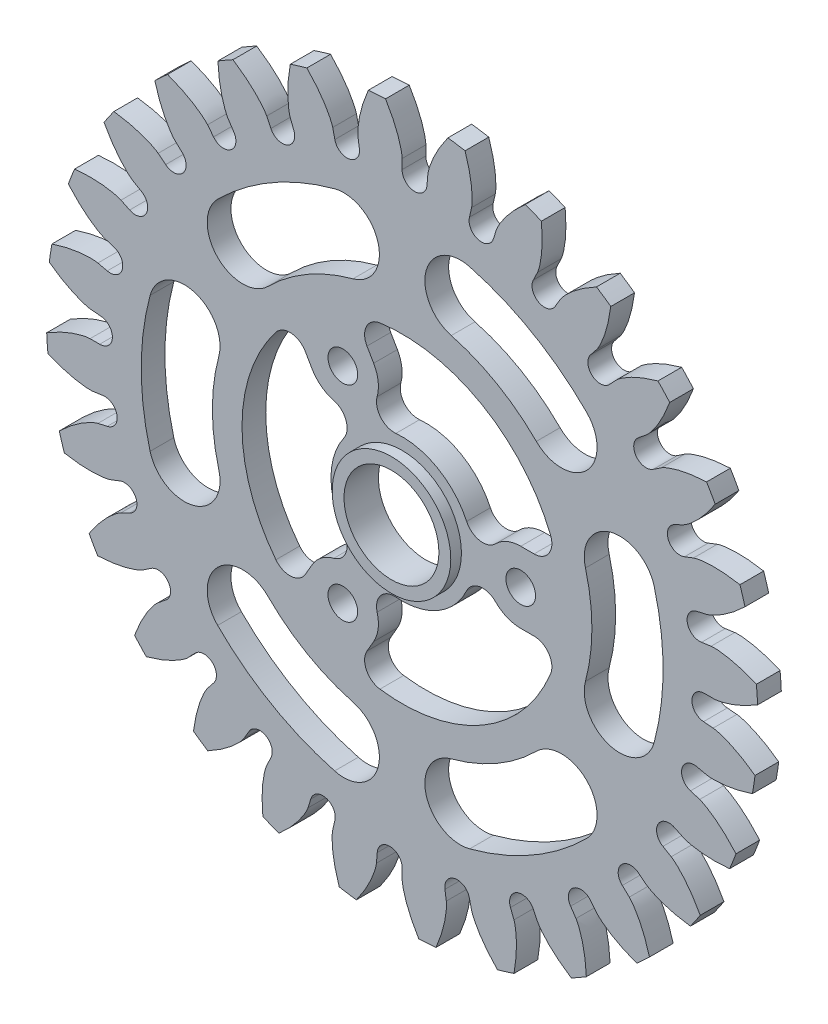
SolidWorks part; units mm, degrees
material "A2017"
ref_plane "正面" through (0, 0, 0) normal (0, 0, 1) x (1, 0, 0)
ref_plane "平面" through (0, 0, 0) normal (0, 1, 0) x (1, 0, 0)
ref_plane "右側面" through (0, 0, 0) normal (1, 0, 0) x (0, 0, -1)
sketch "ｽｹｯﾁ1" plane through (0, 0, 0) normal (1, 0, 0) x (0, 0, -1)
  line L0 (0, 0) -> (5.1985, 0) construction
  line L1 (0, 4) -> (2.9, 4)
  line L2 (2.9, 4) -> (2.9, 17.5)
  line L3 (2.9, 17.5) -> (0.9, 17.5)
  line L4 (0.9, 17.5) -> (0.9, 5)
  line L5 (0.9, 5) -> (0, 5)
  line L6 (0, 5) -> (0, 4)
  dimension "D1" = 35
  dimension "D2" = 2.9
  dimension "D3" = 2
  dimension "D4" = 10
  dimension "D5" = 8
revolve "回転1" add sketch "ｽｹｯﾁ1" angle 360 about L0
hole_wizard "M3 ねじ穴1" positions "ｽｹｯﾁ2" profile "ｽｹｯﾁ3" tap size "M3" standard "JIS" end condition through all
sketch "ｽｹｯﾁ2" plane through (0, 0, -0.9) normal (0, 0, 1) x (1, 0, 0)
  point P0 (10, 0)
  point P3 (-5, 8.6603)
  point P6 (-5, -8.6603)
sketch "ｽｹｯﾁ3" plane through (10, 0, -0.9) normal (1, 0, 0) x (0, -1, 0)
  line L0 (0, 0) -> (0, 2)
  line L1 (0, 2) -> (1.25, 2)
  line L2 (1.25, 2) -> (1.25, 0)
  line L5 (1.25, 0) -> (0, 0)
  line L11 (0, -6.35) -> (0, 107.95) construction
  dimension "次ｻｰﾌｪｽまでのねじ下穴ﾄﾞﾘﾙ直径" = 2.5
  dimension "次ｻｰﾌｪｽまでのねじ下穴ﾄﾞﾘﾙの深さ" = 2
cosmetic thread "穴のねじ山1" parameters "D2"=3
cosmetic thread "穴のねじ山2" parameters "D2"=3
cosmetic thread "穴のねじ山3" parameters "D2"=3
sketch "ｽｹｯﾁ4" plane through (0, 0, -0.9) normal (0, 0, 1) x (1, 0, 0)
  line L0 (10, 0) -> (13.5, 0) construction
  line L1 (10, 3) -> (13.5, 3)
  line L2 (10, -3) -> (13.5, -3)
  line L3 (-5, -8.6603) -> (-6.75, -11.6913) construction
  line L4 (-2.4019, -10.1603) -> (-4.1519, -13.1913)
  line L5 (-7.5981, -7.1603) -> (-9.3481, -10.1913)
  line L6 (-5, 8.6603) -> (-6.75, 11.6913) construction
  line L7 (-7.5981, 7.1603) -> (-9.3481, 10.1913)
  line L8 (-2.4019, 10.1603) -> (-4.1519, 13.1913)
  line L9 (0, 0) -> (10, 0) construction
  circle A0 centre (0, 0) radius 13.5
  arc A1 (10, 3) -> (10, -3) centre (10, 0) ccw
  arc A2 (13.5, -3) -> (13.5, 3) centre (13.5, 0) ccw
  arc A3 (-2.4019, -10.1603) -> (-7.5981, -7.1603) centre (-5, -8.6603) ccw
  arc A4 (-9.3481, -10.1913) -> (-4.1519, -13.1913) centre (-6.75, -11.6913) ccw
  arc A5 (-7.5981, 7.1603) -> (-2.4019, 10.1603) centre (-5, 8.6603) ccw
  arc A6 (-4.1519, 13.1913) -> (-9.3481, 10.1913) centre (-6.75, 11.6913) ccw
  circle A7 centre (0, 0) radius 6
  arc A8 (5.44, 2.5311) -> (7.8667, 2.1092) centre (6.8, 3.1639) ccw
  arc A9 (5.44, -2.5311) -> (7.8667, -2.1092) centre (6.8, -3.1639) cw
  arc A10 (-4.912, -3.4456) -> (-5.76, -5.7581) centre (-6.14, -4.307) cw
  arc A11 (-0.528, -5.9767) -> (-2.1067, -7.8674) centre (-0.66, -7.4709) ccw
  arc A12 (-0.528, 5.9767) -> (-2.1067, 7.8674) centre (-0.66, 7.4709) cw
  arc A13 (-4.912, 3.4456) -> (-5.76, 5.7581) centre (-6.14, 4.307) ccw
  point P6 (11.75, 0)
  point P15 (-5.875, -10.1758)
  point P22 (-5.875, 10.1758)
  point P34 (0, 0)
  point P49 (0, 0)
  dimension "D1" = 27
  dimension "D4" = 12
  dimension "D5" = 3
  dimension "D2" = 6
  dimension "D3" = 3
  dimension "D6" = 3
extrude "ｶｯﾄ - 押し出し1" cut sketch "ｽｹｯﾁ4" against normal through all contours A7 A13 A5 L7 A0 L5 A3 A10 | A12 A7 A8 A1 L1 A0 L8 A5 | A7 A11 A3 L4 A0 L2 A1 A9 region at (4.6223, 8.0061, -0.9) region at (4.6223, -8.0061, -0.9) region at (-9.2446, 0, -0.9)
fillet "ﾌｨﾚｯﾄ1" radius 1.5 6 edges at (13.1624, 3, -1.9) (-9.1793, -9.899, -1.9) (13.1624, -3, -1.9) (-3.9831, -12.899, -1.9) (-9.1793, 9.899, -1.9) (-3.9831, 12.899, -1.9)
sketch "歯車作図" plane through (0, 0, -0.9) normal (0, 0, 1) x (1, 0, 0)
  line L0 (0, 0) -> (25.5, 0) construction
  line L1 (25.5, 0) -> (26.3114, 0)
  line L2 (0, 0) -> (29.9745, -1.2355)
  circle A0 centre (0, 0) radius 30
  circle A1 centre (0, 0) radius 28 construction
  circle A2 centre (0, 0) radius 26.3114 construction
  circle A3 centre (0, 0) radius 25.5 construction
  arc A4 (27.9762, -1.1531) -> (27.9969, 0.4173) centre (0, 0) ccw
  spline S0 degree 4 poles (26.3114, 0) (26.3519, 0.0013) (26.4329, 0.0063) (26.6589, 0.033) (27.0848, 0.1166) (27.7247, 0.3006) (28.5755, 0.6367) (29.6254, 1.1673) (30.7905, 1.9033) (31.9912, 2.8259) (33.1927, 3.9303) (34.3032, 5.1257) (35.3247, 6.3978) (36.3053, 7.8011) (37.4014, 9.6156) (38.528, 11.8801) (39.5864, 14.6214) (40.4562, 17.7686) (41.0337, 20.9817) (41.3324, 24.232) (41.3656, 27.4956) (41.1738, 30.3444) (40.8594, 32.7708) (40.5015, 34.7769) (40.1586, 36.3716) (39.762, 37.9517) (39.3106, 39.5208) (38.8102, 41.0681) (38.3238, 42.4169) (37.8838, 43.5452) (37.5131, 44.4365) (37.2634, 45.0171) (36.9734, 45.666) (36.7803, 46.0867) (36.463, 46.7613) (36.2065, 47.2825) (35.8912, 47.9127) (35.6004, 48.4699) (35.2823, 49.0677) (34.9714, 49.6307) (34.7238, 50.0704) (34.5624, 50.3492) (34.4786, 50.4938) knots 0 0 0 0 0 0.002802 0.005604 0.015718 0.02996 0.048734 0.068727 0.096889 0.125051 0.153212 0.181374 0.209535 0.237696 0.271429 0.327752 0.384075 0.440398 0.496721 0.553044 0.609367 0.66569 0.693852 0.722013 0.750174 0.778336 0.806497 0.834659 0.86282 0.876901 0.890982 0.900036 0.909091 0.920455 0.931818 0.943182 0.954545 0.965909 0.977273 0.988636 1 1 1 1 1 construction
  spline S1 degree 4 poles (26.3114, 0) (26.3519, 0.0013) (26.4329, 0.0063) (26.6589, 0.033) (27.0848, 0.1166) (27.7247, 0.3006) (28.5755, 0.6367) (29.6254, 1.1673) (30.7905, 1.9033) (31.9912, 2.8259) (33.1927, 3.9303) (34.3032, 5.1257) (35.3247, 6.3978) (36.3053, 7.8011) (37.4014, 9.6156) (38.528, 11.8801) (39.5864, 14.6214) (40.4562, 17.7686) (41.0337, 20.9817) (41.3324, 24.232) (41.3656, 27.4956) (41.1738, 30.3444) (40.8594, 32.7708) (40.5015, 34.7769) (40.1586, 36.3716) (39.762, 37.9517) (39.3106, 39.5208) (38.8102, 41.0681) (38.3238, 42.4169) (37.8838, 43.5452) (37.5131, 44.4365) (37.2634, 45.0171) (37.049, 45.4967) (36.9499, 45.7154) (36.9004, 45.8237) knots 0 0 0 0 0 0.002802 0.005604 0.015718 0.02996 0.048734 0.068727 0.096889 0.125051 0.153212 0.181374 0.209535 0.237696 0.271429 0.327752 0.384075 0.440398 0.496721 0.553044 0.609367 0.66569 0.693852 0.722013 0.750174 0.778336 0.806497 0.834659 0.86282 0.876901 0.890982 0.900036 0.909091 0.909091 0.909091 0.909091 0.909091
  point P12 (0, 0)
  point P13 (29.9967, 0.4471)
  point P16 (0, 0)
  point P17 (29.9967, -1.5884)
  dimension "歯先円直径" = 60
  dimension "基礎ピッチ円直径" = 56
  dimension "基礎円直径" = 52.6228
  dimension "全歯丈" = 4.5
  dimension "基準ピッチ" = 1.5708
sketch "ｽｹｯﾁ6" plane through (0, 0, -0.9) normal (0, 0, 1) x (1, 0, 0)
  circle A0 centre (0, 0) radius 30 construction
  circle A1 centre (0, 0) radius 30
  circle A3 centre (0, 0) radius 17.5
  circle A4 centre (0, 0) radius 17.5
  dimension "D1" = 0
extrude "ﾎﾞｽ - 押し出し1" add sketch "ｽｹｯﾁ6" against normal through all
sketch "ｽｹｯﾁ7" plane through (0, 0, -0.9) normal (0, 0, 1) x (1, 0, 0)
  line L0 (25.5, 0) -> (26.3114, 0) construction
  line L1 (0, 0) -> (29.9745, -1.2355) construction
  line L2 (25.5, 0) -> (26.3114, 0)
  line L3 (25.4784, -1.0502) -> (29.9745, -1.2355)
  circle A1 centre (0, 0) radius 30
  arc A2 (29.9745, -1.2355) -> (29.9674, 1.3986) centre (0, 0) ccw
  circle A3 centre (0, 0) radius 25.5 construction
  arc A4 (25.4784, -1.0502) -> (25.5, 0) centre (0, 0) ccw
  spline S0 degree 4 poles (18.0064, -999.7701) (20.0439, 38.1516) (22.4374, 0.7712) (24.776, -0.3364) (27.0848, 0.1166) (27.7247, 0.3006) (28.5755, 0.6367) (29.6254, 1.1673) (30.7905, 1.9033) (31.9912, 2.8259) (33.1927, 3.9303) (34.3032, 5.1257) (35.3247, 6.3978) (36.3053, 7.8011) (37.4014, 9.6156) (38.528, 11.8801) (39.5864, 14.6214) (40.4562, 17.7686) (41.0337, 20.9817) (41.3324, 24.232) (41.3656, 27.4956) (41.1738, 30.3444) (40.8594, 32.7708) (40.5015, 34.7769) (40.1586, 36.3716) (39.762, 37.9517) (39.3106, 39.5208) (38.8102, 41.0681) (38.3238, 42.4169) (37.8838, 43.5452) (37.5131, 44.4365) (36.5867, 46.5912) (34.7604, 50.3825) (49.4042, 17.9493) (-379.6911, 954.9172) knots -0.132452 -0.132452 -0.132452 -0.132452 -0.132452 0.002802 0.005604 0.015718 0.02996 0.048734 0.068727 0.096889 0.125051 0.153212 0.181374 0.209535 0.237696 0.271429 0.327752 0.384075 0.440398 0.496721 0.553044 0.609367 0.66569 0.693852 0.722013 0.750174 0.778336 0.806497 0.834659 0.86282 0.876901 0.890982 0.900036 1.034522 1.034522 1.034522 1.034522 1.034522 only from (26.3114, 0) to (36.9004, 45.8237) construction
  spline S1 degree 4 poles (26.3114, 0) (26.3519, 0.0013) (26.4329, 0.0063) (26.6589, 0.033) (27.0848, 0.1166) (27.7247, 0.3006) (28.5683, 0.6339) (29.2472, 0.9762) (29.727, 1.252) (29.9674, 1.3986) knots 0 0 0 0 0 0.002802 0.005604 0.015718 0.02996 0.048734 0.06819 0.06819 0.06819 0.06819 0.06819
  dimension "D1" = 0
extrude "ｶｯﾄ - 押し出し2" cut sketch "ｽｹｯﾁ7" against normal through all
pattern_circular "円形ﾊﾟﾀｰﾝ1" count 28 over 360 about axis through (0, 0, 0) along (0, 0, 1) of "ｶｯﾄ - 押し出し2"
mirror "ﾐﾗｰ1" about plane through (25.4784, -1.0502, -2.9) normal (-0.0412, -0.9992, 0) of "円形ﾊﾟﾀｰﾝ1"
sketch "ｽｹｯﾁ8" plane through (0, 0, -0.9) normal (0, 0, 1) x (1, 0, 0)
  circle A0 centre (1.0502, 25.4784) radius 1.0504
  arc A1 (2.0986, 25.4135) -> (0, 25.5) centre (0, 0) ccw construction
extrude "ｶｯﾄ - 押し出し3" cut sketch "ｽｹｯﾁ8" against normal through all
pattern_circular "円形ﾊﾟﾀｰﾝ2" count 28 over 360 about axis through (0, 0, 0) along (0, 0, 1) of "ｶｯﾄ - 押し出し3"
sketch "ｽｹｯﾁ9" plane through (0, 0, -0.9) normal (0, 0, 1) x (1, 0, 0)
  line L0 (0, 0) -> (19, 0) construction
  line L1 (0, 0) -> (18.3526, -4.9176) construction
  line L2 (18.3526, 4.9176) -> (0, 0) construction
  circle A0 centre (0, 0) radius 16 construction
  circle A1 centre (0, 0) radius 22 construction
  arc A2 (18.3526, -4.9176) -> (18.3526, 4.9176) centre (0, 0) ccw construction
  arc A3 (21.2504, -5.694) -> (21.2504, 5.694) centre (0, 0) ccw
  arc A4 (15.4548, -4.1411) -> (15.4548, 4.1411) centre (0, 0) ccw
  arc A5 (15.4548, -4.1411) -> (21.2504, -5.694) centre (18.3526, -4.9176) ccw
  arc A6 (21.2504, 5.694) -> (15.4548, 4.1411) centre (18.3526, 4.9176) ccw
  arc A7 (4.9176, -18.3526) -> (13.435, -13.435) centre (0, 0) ccw construction
  arc A8 (5.694, -21.2504) -> (15.5563, -15.5563) centre (0, 0) ccw
  arc A9 (4.1411, -15.4548) -> (11.3137, -11.3137) centre (0, 0) ccw
  arc A10 (4.1411, -15.4548) -> (5.694, -21.2504) centre (4.9176, -18.3526) ccw
  arc A11 (15.5563, -15.5563) -> (11.3137, -11.3137) centre (13.435, -13.435) ccw
  arc A12 (-13.435, -13.435) -> (-4.9176, -18.3526) centre (0, 0) ccw construction
  arc A13 (-15.5563, -15.5563) -> (-5.694, -21.2504) centre (0, 0) ccw
  arc A14 (-11.3137, -11.3137) -> (-4.1411, -15.4548) centre (0, 0) ccw
  arc A15 (-11.3137, -11.3137) -> (-15.5563, -15.5563) centre (-13.435, -13.435) ccw
  arc A16 (-5.694, -21.2504) -> (-4.1411, -15.4548) centre (-4.9176, -18.3526) ccw
  arc A17 (-18.3526, 4.9176) -> (-18.3526, -4.9176) centre (0, 0) ccw construction
  arc A18 (-21.2504, 5.694) -> (-21.2504, -5.694) centre (0, 0) ccw
  arc A19 (-15.4548, 4.1411) -> (-15.4548, -4.1411) centre (0, 0) ccw
  arc A20 (-15.4548, 4.1411) -> (-21.2504, 5.694) centre (-18.3526, 4.9176) ccw
  arc A21 (-21.2504, -5.694) -> (-15.4548, -4.1411) centre (-18.3526, -4.9176) ccw
  arc A22 (-4.9176, 18.3526) -> (-13.435, 13.435) centre (0, 0) ccw construction
  arc A23 (-5.694, 21.2504) -> (-15.5563, 15.5563) centre (0, 0) ccw
  arc A24 (-4.1411, 15.4548) -> (-11.3137, 11.3137) centre (0, 0) ccw
  arc A25 (-4.1411, 15.4548) -> (-5.694, 21.2504) centre (-4.9176, 18.3526) ccw
  arc A26 (-15.5563, 15.5563) -> (-11.3137, 11.3137) centre (-13.435, 13.435) ccw
  arc A27 (13.435, 13.435) -> (4.9176, 18.3526) centre (0, 0) ccw construction
  arc A28 (15.5563, 15.5563) -> (5.694, 21.2504) centre (0, 0) ccw
  arc A29 (11.3137, 11.3137) -> (4.1411, 15.4548) centre (0, 0) ccw
  arc A30 (11.3137, 11.3137) -> (15.5563, 15.5563) centre (13.435, 13.435) ccw
  arc A31 (5.694, 21.2504) -> (4.1411, 15.4548) centre (4.9176, 18.3526) ccw
  point P6 (19, 0)
  point P20 (9.5, -16.4545)
  point P27 (-9.5, -16.4545)
  point P34 (-19, 0)
  point P41 (-9.5, 16.4545)
  point P48 (9.5, 16.4545)
  point P53 (0, 0)
  dimension "D1" = 32
  dimension "D2" = 44
  dimension "D3" = 6
  dimension "D4" = 30
  dimension "D5" = 6
extrude "ｶｯﾄ - 押し出し4" cut sketch "ｽｹｯﾁ9" against normal through all
equation "\"モジュール\"= 2"
equation "\"歯数\"= 28"
equation "\"圧力角\"= 20"
equation "\"歯先円直径@歯車作図\" =  ( \"歯数\" + 2 )  * \"モジュール\""
equation "\"基礎ピッチ円直径@歯車作図\" = \"モジュール\" * \"歯数\""
equation "\"基礎円直径@歯車作図\" = \"歯数\" * \"モジュール\" * cos ( \"圧力角\" ) "
equation "\"全歯丈@歯車作図\" = 2.25 * \"モジュール\""
equation "\"基準ピッチ@歯車作図\" = PI * \"モジュール\" / 4"
equation "\"D1@円形ﾊﾟﾀｰﾝ1\"=\"歯数\""
equation "\"D1@円形ﾊﾟﾀｰﾝ2\"=\"歯数\""
